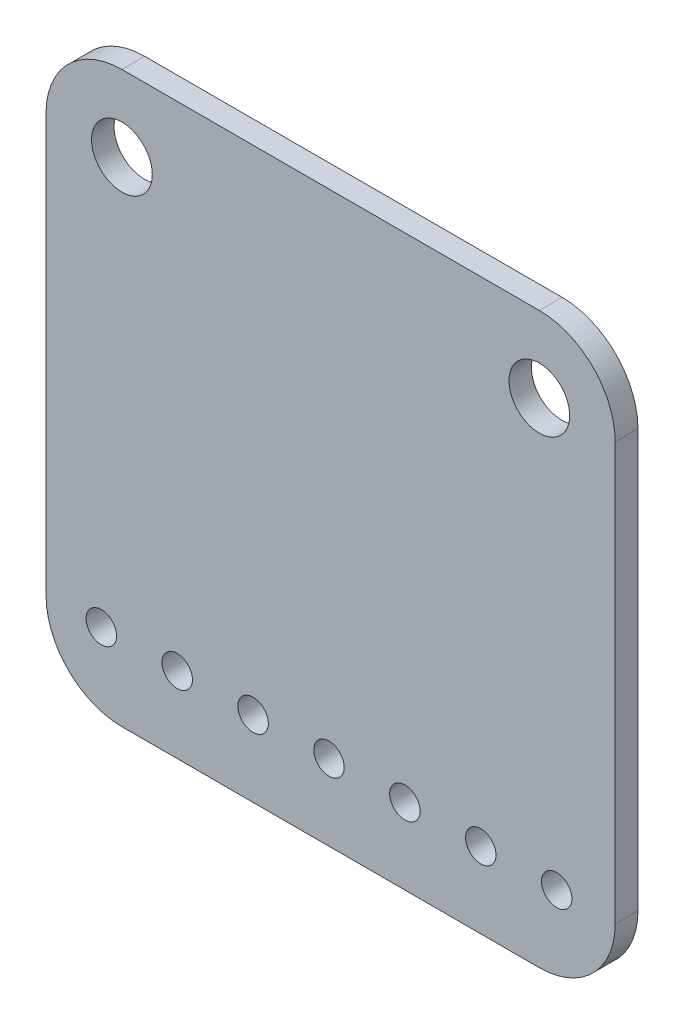
SolidWorks part; units mm, degrees
ref_plane "Ön Düzlem" through (0, 0, 0) normal (0, 0, 1) x (1, 0, 0)
ref_plane "Üst Düzlem" through (0, 0, 0) normal (0, 1, 0) x (1, 0, 0)
ref_plane "Sağ Düzlem" through (0, 0, 0) normal (1, 0, 0) x (0, 0, -1)
sketch "Çizim1" plane through (0, 0, 0) normal (0, 0, 1) x (1, 0, 0)
  line L0 (2.54, 0) -> (16.51, 0)
  line L1 (19.05, 2.54) -> (19.05, 16.51)
  line L2 (16.51, 19.05) -> (2.54, 19.05)
  line L3 (0, 16.51) -> (0, 2.54)
  arc A0 (0, 16.51) -> (2.54, 19.05) centre (2.54, 16.51) cw
  arc A1 (2.54, 0) -> (0, 2.54) centre (2.54, 2.54) cw
  arc A2 (19.05, 2.54) -> (16.51, 0) centre (16.51, 2.54) cw
  arc A3 (16.51, 19.05) -> (19.05, 16.51) centre (16.51, 16.51) cw
  point P7 (0, 19.05)
  point P10 (0, 0)
  point P15 (19.05, 19.05)
  dimension "D3" = 2.54
  dimension "D4" = 2.54
  dimension "D5" = 2.54
  dimension "D6" = 2.54
  dimension "D1" = 19.05
  dimension "D2" = 19.05
extrude "Yükseklik-Ekstrüzyon1" add sketch "Çizim1" along normal blind 0.762
sketch "Çizim2" plane through (0, 0, 0.762) normal (0, 0, 1) x (1, 0, 0)
  line L0 (2.54, 0) -> (16.51, 0) construction
  line L1 (19.05, 2.54) -> (19.05, 16.51) construction
  line L2 (0, 16.51) -> (0, 2.54) construction
  circle A0 centre (16.51, 16.51) radius 1.016
  circle A1 centre (2.54, 16.51) radius 1.016
  dimension "D1" = 2.032
  dimension "D2" = 16.51
  dimension "D3" = 2.54
  dimension "D4" = 13.97
  dimension "D5" = 2.54
extrude "Kes-Ekstrüzyon1" cut sketch "Çizim2" against normal up to next
sketch "Çizim3" plane through (0, 0, 0.762) normal (0, 0, 1) x (1, 0, 0)
  line L1 (2.54, 0) -> (16.51, 0) construction
  circle A0 centre (1.8507, 2.54) radius 0.51
  circle A1 centre (4.3907, 2.54) radius 0.51
  circle A2 centre (6.9307, 2.54) radius 0.51
  circle A3 centre (9.4707, 2.54) radius 0.51
  circle A4 centre (12.0107, 2.54) radius 0.51
  circle A5 centre (14.5507, 2.54) radius 0.51
  circle A6 centre (17.0907, 2.54) radius 0.51
  dimension "D1" = 1.02
  dimension "D3" = 2.54
  dimension "D2" = 7
extrude "Kes-Ekstrüzyon2" cut sketch "Çizim3" against normal up to next
sketch "Çizim4" plane through (0, 0, 0) normal (0, 0, -1) x (-1, 0, 0)
  circle A0 centre (-16.51, 16.51) radius 1.5
extrude "Kes-Ekstrüzyon3" cut sketch "Çizim4" against normal blind 0.01
sketch "Çizim5" plane through (0, 0, 0) normal (0, 0, -1) x (-1, 0, 0)
  circle A1 centre (-2.54, 16.51) radius 1.5
  dimension "D1" = 3
extrude "Kes-Ekstrüzyon4" cut sketch "Çizim5" against normal blind 0.01
sketch "Çizim6" plane through (0, 0, 0) normal (0, 0, -1) x (-1, 0, 0)
  circle A0 centre (-17.0907, 2.54) radius 0.75
extrude "Kes-Ekstrüzyon5" cut sketch "Çizim6" against normal blind 0.01
sketch "Çizim7" plane through (0, 0, 0) normal (0, 0, -1) x (-1, 0, 0)
  circle A0 centre (-14.5507, 2.54) radius 0.75
  circle A1 centre (-12.0107, 2.54) radius 0.75
  circle A2 centre (-9.4707, 2.54) radius 0.75
  circle A3 centre (-6.9307, 2.54) radius 0.75
  circle A4 centre (-4.3907, 2.54) radius 0.75
  circle A5 centre (-1.8507, 2.54) radius 0.75
  dimension "D1" = 6
extrude "Kes-Ekstrüzyon6" cut sketch "Çizim7" against normal blind 0.01
sketch "Çizim8" plane through (0, 0, 0) normal (0, 0, -1) x (-1, 0, 0)
  line L0 (-13.3396, 16.2124) -> (-4.4043, 16.2124) construction
  text T0 "ADXL335" font "Century Gothic" height in points 5
extrude "Yükseklik-Ekstrüzyon2" add sketch "Çizim8" along normal blind 0.1
sketch "Çizim9" plane through (0, 0, 0) normal (0, 0, -1) x (-1, 0, 0)
  line L0 (-18.0063, 3.7727) -> (-0.964, 3.7727) construction
  text T0 "Vin        3Vo     GND    Zout    Yout      Xout     Test" font "Century Gothic" height in points 2
extrude "Yükseklik-Ekstrüzyon4" add sketch "Çizim9" along normal blind 0.1
sketch "Çizim11" plane through (0, 0, 0) normal (0, 0, -1) x (-1, 0, 0)
  line L0 (-12.171, 14.1515) -> (-7.1366, 14.1515)
  line L1 (-7.1366, 14.1515) -> (-7.1366, 9.0137)
  line L2 (-7.1366, 9.0137) -> (-12.171, 9.0137)
  line L3 (-12.171, 9.0137) -> (-12.171, 14.1515)
extrude "Yükseklik-Ekstrüzyon5" add sketch "Çizim11" along normal blind 0.6
sketch "Çizim12" plane through (0, 0, 0) normal (0, 0, -1) x (-1, 0, 0)
  line L1 (-17.2587, 10.0301) -> (-14.541, 10.0301)
  line L2 (-17.2587, 10.0301) -> (-17.2587, 8.7088)
  line L3 (-17.2587, 8.7088) -> (-14.541, 8.7088)
  line L4 (-14.541, 10.0301) -> (-14.541, 8.7088)
extrude "Yükseklik-Ekstrüzyon6" add sketch "Çizim12" along normal blind 0.4
sketch "Çizim13" plane through (0, 0, 0) normal (0, 0, -1) x (-1, 0, 0)
  line L1 (-13.2443, 8.1902) -> (-10.5566, 8.1902)
  line L2 (-13.2443, 8.1902) -> (-13.2443, 6.8989)
  line L3 (-13.2443, 6.8989) -> (-10.5566, 6.8989)
  line L4 (-10.5566, 8.1902) -> (-10.5566, 6.8989)
  line L5 (-8.7998, 8.1902) -> (-6.0971, 8.1902)
  line L6 (-8.7998, 8.1902) -> (-8.7998, 6.8989)
  line L7 (-8.7998, 6.8989) -> (-6.0971, 6.8989)
  line L8 (-6.0971, 8.1902) -> (-6.0971, 6.8989)
  line L9 (-4.7908, 8.1902) -> (-2.2532, 8.1902)
  line L10 (-4.7908, 8.1902) -> (-4.7908, 6.8989)
  line L11 (-4.7908, 6.8989) -> (-2.2532, 6.8989)
  line L12 (-2.2532, 8.1902) -> (-2.2532, 6.8989)
extrude "Yükseklik-Ekstrüzyon7" add sketch "Çizim13" along normal blind 0.4
sketch "Çizim14" plane through (0, 0, 0) normal (0, 0, -1) x (-1, 0, 0)
  line L1 (-5.1052, 10.5252) -> (-2.3555, 10.5252)
  line L2 (-5.1052, 10.5252) -> (-5.1052, 9.2588)
  line L3 (-5.1052, 9.2588) -> (-2.3555, 9.2588)
  line L4 (-2.3555, 10.5252) -> (-2.3555, 9.2588)
extrude "Yükseklik-Ekstrüzyon8" add sketch "Çizim14" along normal blind 0.4
sketch "Çizim15" plane through (0, 0, 0) normal (0, 0, -1) x (-1, 0, 0)
  line L1 (-16.402, 10.8737) -> (-14.39, 10.8737)
  line L2 (-16.402, 10.8737) -> (-16.402, 13.8467)
  line L3 (-16.402, 13.8467) -> (-14.39, 13.8467)
  line L4 (-14.39, 10.8737) -> (-14.39, 13.8467)
extrude "Yükseklik-Ekstrüzyon9" add sketch "Çizim15" along normal blind 0.5
